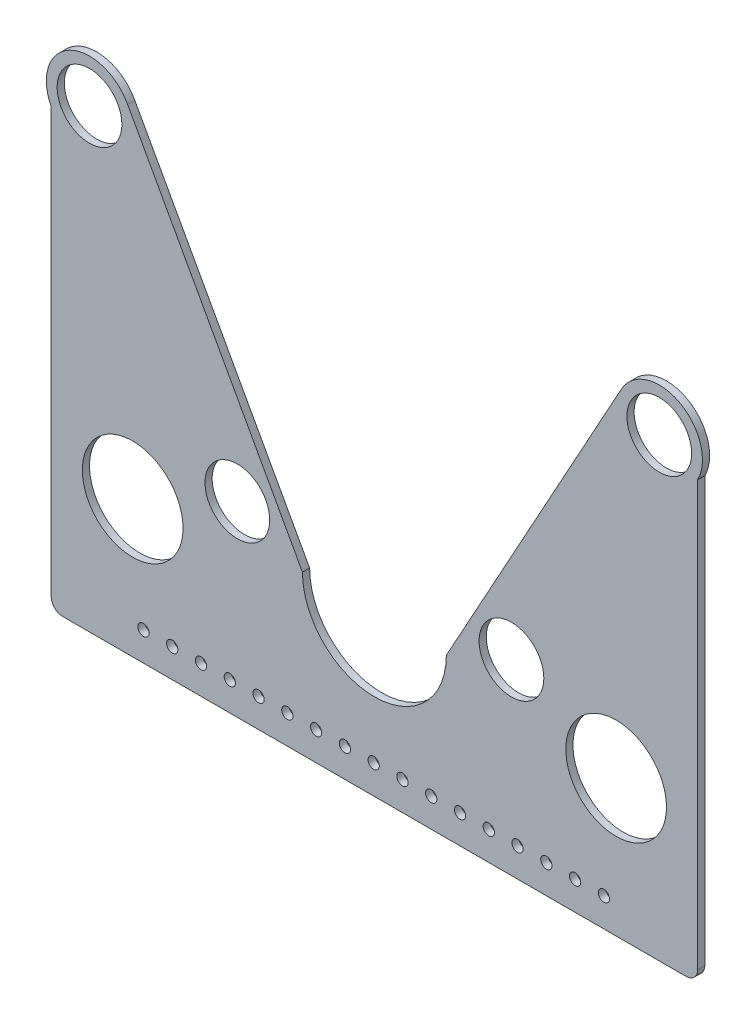
SolidWorks part; units mm, degrees
ref_plane "Front Plane" through (0, 0, 0) normal (0, 0, 1) x (1, 0, 0)
ref_plane "Top Plane" through (0, 0, 0) normal (0, 1, 0) x (1, 0, 0)
ref_plane "Right Plane" through (0, 0, 0) normal (1, 0, 0) x (0, 0, -1)
sketch "Sketch2" plane through (0, 0, 0) normal (0, 0, 1) x (1, 0, 0)
  line L0 (-142.6324, -29.9371) -> (-142.6324, -64.77)
  line L1 (142.6324, 122.4629) -> (142.6324, -29.9371)
  line L3 (31.75, 0) -> (108.9183, 140.209)
  line L4 (0, -1082.0685) -> (0, 1082.0685) construction
  line L5 (-106.68, -44.45) -> (106.68, -44.45) construction
  line L6 (-106.68, -59.1767) -> (-106.68, -31.75)
  line L7 (0, -31.75) -> (106.68, -31.75) construction
  line L8 (106.68, -55.9582) -> (106.68, -31.75)
  line L9 (-31.75, 0) -> (-108.9183, 140.209)
  line L10 (31.75, 0) -> (108.9183, 140.209)
  line L11 (142.6324, -64.77) -> (142.6324, -29.9371)
  line L33 (-106.68, -31.75) -> (0, -31.75) construction
  line L34 (-142.6324, 122.4629) -> (-142.6324, -29.9371)
  line L35 (137.5524, -69.85) -> (-137.5524, -69.85)
  arc A0 (-31.75, 0) -> (31.75, 0) centre (0, 0) ccw
  arc A1 (-108.9183, 140.209) -> (-142.6324, 122.4629) centre (-125.7268, 131.2438) ccw
  circle A2 centre (-60.4845, 12.7) radius 14.2875
  arc A3 (31.75, 0) -> (0, 31.75) centre (0, 0) ccw construction
  arc A4 (0, 31.75) -> (-31.75, 0) centre (0, 0) ccw construction
  arc A5 (137.5524, -69.85) -> (142.6324, -64.77) centre (137.5524, -64.77) ccw
  arc A6 (-137.5524, -69.85) -> (-142.6324, -64.77) centre (-137.5524, -64.77) cw
  circle A7 centre (-125.7268, 131.2438) radius 14.2875
  circle A9 centre (-60.4845, 12.7) radius 19.05 construction
  circle A10 centre (60.4845, 12.7) radius 19.05 construction
  arc A11 (108.9183, 140.209) -> (142.6324, 122.4629) centre (125.7268, 131.2438) cw
  circle A12 centre (125.7268, 131.2438) radius 14.2875
  circle A34 centre (-101.9175, -57.15) radius 2.4892
  arc A40 (-142.6324, 122.4629) -> (-108.9183, 140.209) centre (-125.7268, 131.2438) ccw construction
  arc A41 (142.6324, 122.4629) -> (108.9183, 140.209) centre (125.7268, 131.2438) cw construction
  circle A42 centre (60.4845, 12.7) radius 14.2875
  circle A43 centre (-89.2175, -57.15) radius 2.4892
  circle A44 centre (-76.5175, -57.15) radius 2.4892
  circle A45 centre (-63.8175, -57.15) radius 2.4892
  circle A46 centre (-51.1175, -57.15) radius 2.4892
  circle A47 centre (-38.4175, -57.15) radius 2.4892
  circle A48 centre (-25.7175, -57.15) radius 2.4892
  circle A49 centre (-13.0175, -57.15) radius 2.4892
  circle A50 centre (-0.3175, -57.15) radius 2.4892
  circle A51 centre (12.3825, -57.15) radius 2.4892
  circle A52 centre (25.0825, -57.15) radius 2.4892
  circle A53 centre (37.7825, -57.15) radius 2.4892
  circle A54 centre (50.4825, -57.15) radius 2.4892
  circle A55 centre (63.1825, -57.15) radius 2.4892
  circle A56 centre (75.8825, -57.15) radius 2.4892
  circle A57 centre (88.5825, -57.15) radius 2.4892
  circle A58 centre (101.2825, -57.15) radius 2.4892
  circle A71 centre (-106.68, -9.525) radius 22.225
  circle A72 centre (106.68, -9.525) radius 22.225
  point P0 (142.6324, -68.7497)
  dimension "D7" = 131.2438
  dimension "D8" = 9.525
  dimension "D9" = 25.4
  dimension "D3" = 44.45
  dimension "D14" = 106.68
  dimension "D17" = 38.1
  dimension "D5" = 12.7
  dimension "D15" = 31.75
  dimension "D16" = 28.575
  dimension "D18" = 28.575
  dimension "D19" = 19.05
  dimension "D21" = 125.7268
  dimension "D27" = 44.45
  dimension "D4" = 5.08
  dimension "D1" = 28.828
  dimension "D6" = 101.9175
  dimension "D10" = 17
  dimension "D20" = 142.6324
  dimension "D25" = 152.4
  dimension "D26" = 12.7
extrude "Boss-Extrude1" add sketch "Sketch2" along normal blind 3.175 contours A11 L3 A0 L9 A1 L6 L8 A58 A57 A56 A55 region at (-138.995, 46.2629, 0)
